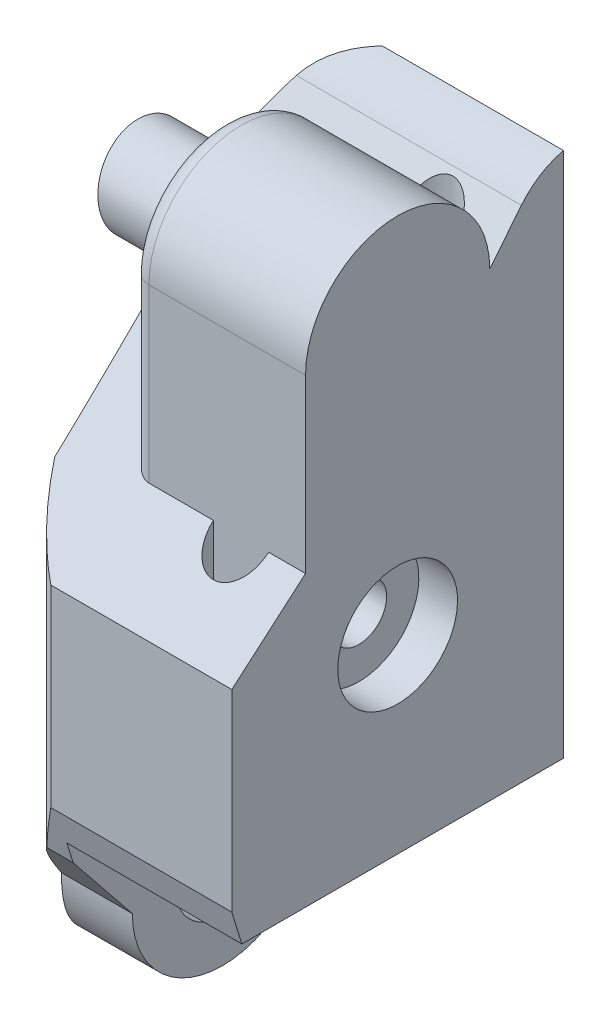
SolidWorks part; units mm, degrees
ref_plane "Front Plane" through (0, 0, 0) normal (0, 0, 1) x (1, 0, 0)
ref_plane "Top Plane" through (0, 0, 0) normal (0, 1, 0) x (1, 0, 0)
ref_plane "Right Plane" through (0, 0, 0) normal (1, 0, 0) x (0, 0, -1)
sketch "Sketch1" plane through (0, 0, 0) normal (0, 1, 0) x (1, 0, 0)
  line L0 (-6.3246, 9) -> (6.3246, 9)
  line L1 (-6.3246, -9) -> (6.3246, -9)
  arc A0 (-6.3246, 9) -> (-6.3246, -9) centre (0, 0) ccw
  arc A1 (6.3246, 9) -> (6.3246, -9) centre (0, 0) cw
  point P9 (-11, 0)
  point P10 (11, 0)
  dimension "D1" = 22
  dimension "D2" = 18
extrude "Boss-Extrude1" add sketch "Sketch1" along normal blind 40
sketch "Sketch2" plane through (0, 0, 0) normal (0, -1, 0) x (1, 0, 0)
  line L0 (1.5, 5) -> (-1.5, 5)
  line L1 (1.5, -5) -> (-1.5, -5)
  line L2 (0, -5) -> (0, 5) construction
  arc A2 (-1.5, 5) -> (1.5, 5) centre (0, 5) cw
  arc A3 (-1.5, -5) -> (1.5, -5) centre (0, -5) ccw
  dimension "D1" = 1.5
  dimension "D2" = 10
extrude "Cut-Extrude1" cut sketch "Sketch2" against normal blind 58
sketch "Sketch3" plane through (0, 0, -9) normal (0, 0, -1) x (-1, 0, 0)
  line L0 (6, 0) -> (6, 10)
  line L1 (6, 10) -> (-6, 10)
  line L2 (-6, 10) -> (-6, 0)
  line L3 (6, 0) -> (-6, 0)
  line L4 (-6.3246, 0) -> (6.3246, 0) construction
  point P10 (0, 0)
  dimension "D1" = 12
  dimension "D2" = 10
extrude "Cut-Extrude2" cut sketch "Sketch3" against normal up to surface (18 mm away) up to face at (0, 20, 9)
sketch "Sketch4" plane through (6, 0, 0) normal (-1, 0, 0) x (0, 0, 1)
  line L0 (-9, 10) -> (-4.9, 4.9)
  line L1 (9, 10) -> (4.9, 4.9)
  line L2 (9, 0) -> (-9, 0) construction
  line L3 (-9, 10) -> (-10.2904, -1.9304)
  line L4 (-10.2904, -1.9304) -> (12.0438, -1.9304)
  line L6 (9, 40) -> (9, 0) construction
  line L7 (12.0438, -1.9304) -> (9, 10)
  line L8 (-9, 40) -> (-9, 0) construction
  arc A0 (-4.9, 4.9) -> (4.9, 4.9) centre (0, 4.9) ccw
  circle A1 centre (0, 4.9) radius 2.55
  point P7 (0, 0)
  dimension "D1" = 5.1
  dimension "D2" = 4.9
  dimension "D3" = 10
extrude "Cut-Extrude3" cut sketch "Sketch4" against normal mid plane 35
fillet "Fillet4" radius 2 4 edges at (0, 10, 6.5) (0, 10, 5) (0, 10, -5) (0, 10, -6.5)
ref_plane "Plane1" through (-6.3246, 0, 0) normal (-1, 0, 0) x (0, 0, 1)
sketch "Sketch6" plane through (-6.3246, 0, 0) normal (-1, 0, 0) x (0, 0, 1)
  line L0 (9, 22.2324) -> (0, 30)
  line L1 (9, 40) -> (9, 10) construction
  line L2 (-5, 35) -> (-6.7156, 37.1341)
  line L3 (9, 40) -> (-9, 40) construction
  line L7 (-9, 38.5679) -> (-20.9852, 70.2973)
  line L8 (4.9, 4.9) -> (9, 10) construction
  line L9 (-9, 10) -> (-4.9, 4.9) construction
  line L10 (-9, 40) -> (-9, 10) construction
  line L11 (-20.9852, 70.2973) -> (29.8275, 37.5947)
  line L12 (29.8275, 37.5947) -> (9, 22.2324)
  arc A0 (0, 30) -> (-5, 35) centre (0, 35) cw
  circle A1 centre (0, 35) radius 2.5
  arc A2 (-6.7156, 37.1341) -> (-9, 38.5679) centre (-9.9296, 34.5502) ccw
  point P7 (0, 0)
  point P8 (0, 0)
  point P10 (0, 0)
  point P13 (0, 0)
  dimension "D1" = 5
  dimension "D3" = 5
  dimension "D2" = 5
  dimension "D4" = 9
  dimension "D5" = 92
  dimension "D6" = 1.4321
  dimension "D7" = 2.7382
extrude "Cut-Extrude5" cut sketch "Sketch6" against normal blind 9.6 from surface starting at face at (6, 4.9, -2.55)
extrude "Cut-Extrude6" cut sketch "Sketch6<3>" along normal blind 6.604 from surface starting at face at (-6, 4.9, 2.55)
sketch "Sketch6<3>" plane through (-6.3246, 0, 0) normal (-1, 0, 0) x (0, 0, 1) same geometry as "Sketch6"
sketch "Sketch7" plane through (6, 0, 0) normal (1, 0, 0) x (0, 0, -1)
  line L0 (5, 35) -> (6.7156, 37.1341)
  line L2 (57.758, 25.6846) -> (-30.5791, 55.4868)
  line L4 (-5, 35) -> (-5, 25.6846)
  line L5 (-9, 40) -> (9, 40) construction
  line L6 (-5, 25.6846) -> (-9, 22.2324)
  line L7 (-9, 22.2324) -> (-30.5791, 55.4868)
  line L8 (-9, 22.2324) -> (0, 30) construction
  line L9 (9, 38.5679) -> (57.758, 25.6846)
  arc A0 (5, 35) -> (-5, 35) centre (0, 35) ccw
  arc A1 (6.7156, 37.1341) -> (9, 38.5679) centre (9.9296, 34.5502) cw
  arc A2 (9, 38.5679) -> (6.7156, 37.1341) centre (9.9296, 34.5502) ccw construction
  arc A6 (0, 30) -> (5, 35) centre (0, 35) ccw construction
  point P2 (57.758, 25.6846)
  point P7 (4.486, 36.8886)
  point P11 (5, 35)
  point P12 (5, 35)
  point P13 (4.9678, 35.5485)
  point P15 (0, 0)
  point P24 (4.981, 35.4357)
  point P25 (0, 0)
extrude "Cut-Extrude7" cut sketch "Sketch7" against normal blind 14.986
sketch "Sketch16" plane through (-6.3246, 0, 0) normal (-1, 0, 0) x (0, 0, 1)
  line L0 (8.1133, 8.897) -> (11.5501, 20.0314)
  line L1 (11.5501, 20.0314) -> (18.056, 15.6952)
  line L2 (18.056, 15.6952) -> (16.1561, 2.2816)
  line L3 (16.1561, 2.2816) -> (8.1133, 8.897)
  line L4 (4.9, 4.9) -> (9, 10) construction
  line L5 (9, 22.2324) -> (0, 30) construction
extrude "Cut-Extrude14" cut sketch "Sketch16" against normal blind 20 and the other way blind 10
sketch "Sketch17" plane through (0, 0, 0) normal (0, 0, 1) x (1, 0, 0)
  line L0 (11, 0) -> (21.8204, 52.0067)
  line L1 (21.8204, 52.0067) -> (-19.9815, 54.8367)
  line L2 (-19.9815, 54.8367) -> (-22.1033, 10.057)
  line L3 (-22.1033, 10.057) -> (-11, 0)
  line L4 (6, 40) -> (-6, 40) construction
  line L5 (-11, 40) -> (-14.7764, 42.4766)
  line L6 (-14.7764, 42.4766) -> (-7.1773, 49.8432)
  line L7 (-7.1773, 49.8432) -> (9.0997, 46.4567)
  line L8 (9.0997, 46.4567) -> (16.1014, 37.5486)
  line L9 (16.1014, 37.5486) -> (11, 40)
  arc A0 (-11, 0) -> (-11, 40) centre (-127.2927, 20) ccw
  arc A2 (11, 40) -> (11, 0) centre (127.2927, 20) ccw
  point P3 (11, 40)
  point P15 (0, 0)
  dimension "D1" = 118
sketch "Sketch19" plane through (0, 0, 5) normal (0, 0, 1) x (1, 0, 0)
  line L1 (3.5, 46.979) -> (21.644, 46.979)
  line L2 (3.5, 46.979) -> (3.5, -5.5321)
  line L3 (3.5, -5.5321) -> (21.644, -5.5321)
  line L4 (21.644, 46.979) -> (21.644, -5.5321)
  point P4 (21.644, 46.979)
fillet "Fillet3" radius 1 4 edges at (6, 40, 0) (6, 30.3423, 5) (-6, 40, 0) (-6, 30.3423, 5)
extrude "Cut-Extrude17" cut sketch "Sketch19" against normal blind 31 and the other way blind 9 contours L2 L3 L4 L1
sketch "Sketch20" plane through (3.5, 0, 0) normal (1, 0, 0) x (0, 0, -1)
  line L0 (5, 10) -> (9, 10) construction
  circle A0 centre (0, 20.3) radius 3.25
  dimension "D1" = 6.5
  dimension "D2" = 10.3
extrude "Cut-Extrude18" cut sketch "Sketch20" against normal blind 2.1
sketch "Sketch21" plane through (1.4, 0, 0) normal (1, 0, 0) x (0, 0, -1)
  circle A0 centre (0, 20.3) radius 1.5
  circle A1 centre (0, 20.3) radius 3.25 construction
  dimension "D1" = 3
extrude "Cut-Extrude19" cut sketch "Sketch21" against normal blind 9.1
extrude "Cut-Extrude20" cut sketch "Sketch17" against normal blind 14 and the other way blind 14 contours L2 L3 A0 L5 L6 L7 L8 L9 A2 L0 L1
